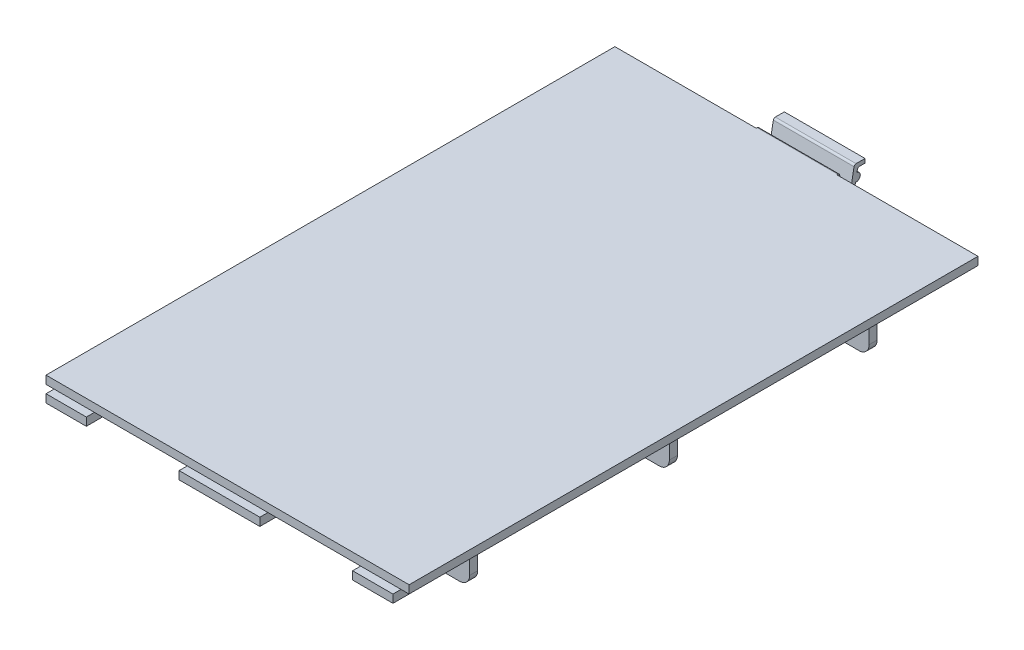
SolidWorks part; units mm, degrees
ref_plane "前视基准面" through (0, 0, 0) normal (0, 0, 1) x (1, 0, 0)
ref_plane "上视基准面" through (0, 0, 0) normal (0, 1, 0) x (1, 0, 0)
ref_plane "右视基准面" through (0, 0, 0) normal (1, 0, 0) x (0, 0, -1)
sketch "Sketch1" plane through (0, 0, 0) normal (0, 1, 0) x (1, 0, 0)
  line L1 (-45, -70.5) -> (45, -70.5)
  line L2 (-45, -70.5) -> (-45, 70.5)
  line L3 (-45, 70.5) -> (45, 70.5)
  line L4 (45, -70.5) -> (45, 70.5)
  line L5 (-45, -70.5) -> (45, 70.5) construction
  line L6 (-45, 70.5) -> (45, -70.5) construction
  point P0 (0, 0)
  dimension "D1" = 141
  dimension "D2" = 90
extrude "Boss-Extrude1" add sketch "Sketch1" along normal blind 2
sketch "Sketch2" plane through (0, 0, 0) normal (0, -1, 0) x (1, 0, 0)
  line L0 (-45, 70.5) -> (45, 70.5) construction
  line L1 (-10, 70.5) -> (10, 70.5)
  line L2 (-10, 70.5) -> (-10, 65.5)
  line L3 (-10, 65.5) -> (10, 65.5)
  line L4 (10, 70.5) -> (10, 65.5)
  line L5 (0, 70.5) -> (0, 40.7579) construction
  line L6 (-43, 70.5) -> (-33, 70.5)
  line L7 (-43, 70.5) -> (-43, 65.5)
  line L8 (-43, 65.5) -> (-33, 65.5)
  line L9 (-33, 70.5) -> (-33, 65.5)
  line L10 (43, 70.5) -> (33, 70.5)
  line L11 (43, 70.5) -> (43, 65.5)
  line L12 (43, 65.5) -> (33, 65.5)
  line L13 (33, 70.5) -> (33, 65.5)
  line L14 (-45, -70.5) -> (-45, 70.5) construction
  line L15 (45, 70.5) -> (45, -70.5) construction
  dimension "D1" = 20
  dimension "D2" = 5
  dimension "D3" = 10
  dimension "D4" = 10
  dimension "D5" = 10
  dimension "D6" = 2
  dimension "D7" = 2
  dimension "D8" = 5
  dimension "D9" = 5
extrude "Boss-Extrude2" add sketch "Sketch2" along normal blind 2
sketch "Sketch3" plane through (0, 0, 70.5) normal (0, 0, 1) x (1, 0, 0)
  line L1 (-43, -2) -> (-33, -2)
  line L2 (-43, -2) -> (-43, 0)
  line L3 (-43, 0) -> (-33, 0)
  line L4 (-33, -2) -> (-33, 0)
  line L5 (-10, -2) -> (10, -2)
  line L6 (-10, -2) -> (-10, 0)
  line L7 (-10, 0) -> (10, 0)
  line L8 (10, -2) -> (10, 0)
  line L9 (33, -2) -> (43, -2)
  line L10 (33, -2) -> (33, 0)
  line L11 (33, 0) -> (43, 0)
  line L12 (43, -2) -> (43, 0)
extrude "Boss-Extrude3" add sketch "Sketch3" along normal blind 2
ref_plane "Plane1" through (0, 0, 0) normal (-1, 0, 0) x (0, 0, 1)
sketch "Sketch4" plane through (0, 0, 0) normal (-1, 0, 0) x (0, 0, 1)
  line L0 (-70.5, 2) -> (-75.5, 2) construction
  line L1 (-73, 2) -> (-73, -7) construction
  line L2 (-72.8177, -7.0168) -> (-71.1463, 2)
  line L3 (-70.5, 0) -> (-72.0126, -8.1596)
  line L4 (-71.1463, 2) -> (-70.5, 2)
  line L5 (-74.8537, 2) -> (-75.5, 2)
  line L6 (-73.1823, -7.0168) -> (-74.8537, 2)
  line L7 (-75.1386, -1.9497) -> (-73.9874, -8.1596)
  line L8 (-77.5, 2) -> (-77.5, 1)
  line L11 (-75.5, 2) -> (-77.5, 2)
  line L13 (-77.5, 1) -> (-75.6854, 1)
  line L14 (-75.5031, 0.0168) -> (-75.6854, 1)
  line L15 (-70.5, 0) -> (-70.5, 2)
  arc A0 (-72.8177, -7.0168) -> (-73.1823, -7.0168) centre (-73, -8) ccw
  arc A1 (-75.5031, 0.0168) -> (-75.1386, -1.9497) centre (-75.3208, -0.9665) ccw
  arc A2 (-72.8177, -7.0165) -> (-73.1823, -7.0165) centre (-73, -8) ccw
  arc A3 (-73.9874, -8.1596) -> (-72.0126, -8.1596) centre (-73, -8) ccw
  point P17 (-73.9874, -8.1596)
  point P18 (-72.0126, -8.1596)
  point P21 (-73, -8)
  dimension "D3" = 2
  dimension "D6" = 2
  dimension "D1" = 5
  dimension "D2" = 10
  dimension "D4" = 1
  dimension "D5" = 2
extrude "Boss-Extrude4" add sketch "Sketch4" along normal mid plane 20 contours L7 A3 L3 L15 L4 L2 A0 L6 L5 L11 L8 L13 L14 A1 region at (0, -7.0404, -72.6895)
fillet "Fillet1" radius 1 1 edges at (0, 0, -70.5)
fillet "Fillet2" radius 0.5 2 edges at (0, 2, -74.8537) (0, 2, -71.1463)
fillet "Fillet3" radius 0.5 1 edges at (0, 1, -75.6854)
sketch "Sketch5" plane through (0, 0, 0) normal (0, -1, 0) x (1, 0, 0)
  line L0 (33, 60.5) -> (33, 50.5)
  line L1 (45, -70.5) -> (10, -70.5) construction
  line L2 (10, 70.5) -> (33, 70.5) construction
  line L3 (-2.5, -1) -> (-28, -1)
  line L4 (33, -50.5) -> (33, -60.5)
  line L5 (0, -81.945) -> (0, -60.5) construction
  line L6 (-33, 70.5) -> (-10, 70.5) construction
  line L7 (-2.5, 60.5) -> (2.5, 60.5)
  line L8 (-2.5, 60.5) -> (-2.5, 49.4375)
  line L9 (-2.5, -60.5) -> (2.5, -60.5)
  line L10 (2.5, 60.5) -> (2.5, 50.5)
  line L11 (-10, -70.5) -> (-45, -70.5) construction
  line L12 (33, -60.5) -> (28, -60.5)
  line L13 (28, -60.5) -> (28, -50.5)
  line L14 (28, 60.5) -> (33, 60.5)
  line L15 (-33, 60.5) -> (-33, 50.325)
  line L16 (-33, -60.5) -> (-28, -60.5)
  line L17 (-28, -60.5) -> (-28, -50.5)
  line L18 (-28, 60.5) -> (-33, 60.5)
  line L19 (45, 0) -> (40, 0) construction
  line L20 (45, 70.5) -> (45, -70.5) construction
  line L21 (-45, -70.5) -> (-45, 70.5) construction
  line L22 (28, -50.5) -> (2.5, -50.5)
  line L23 (40, -1) -> (33, -1)
  line L24 (40, -1) -> (40, 1)
  line L25 (40, 1) -> (33, 1)
  line L26 (-40, -1) -> (-40, 1)
  line L27 (28, -48.5) -> (28, -1)
  line L28 (2.5, -50.5) -> (2.5, -60.5)
  line L29 (40, -50.5) -> (33, -50.5)
  line L30 (40, -50.5) -> (40, -48.5)
  line L31 (40, -48.5) -> (33, -48.5)
  line L32 (-40, -50.5) -> (-40, -48.5)
  line L33 (-33, -50.5) -> (-40, -50.5)
  line L34 (-33, -48.5) -> (-40, -48.5)
  line L35 (40, 48.5) -> (33, 48.5)
  line L36 (40, 48.5) -> (40, 50.5)
  line L37 (40, 50.5) -> (33, 50.5)
  line L38 (-40, 48.5) -> (-40, 50.5)
  line L43 (28, -48.5) -> (2.5, -48.5)
  line L44 (28, -1) -> (2.5, -1)
  line L45 (-2.5, -50.5) -> (-2.5, -60.5)
  line L46 (-28, -48.5) -> (-28, -1)
  line L47 (-33, -50.5) -> (-33, -60.5)
  line L48 (28, 1) -> (2.5, 1)
  line L49 (28, 48.5) -> (2.5, 48.5)
  line L50 (-2.5, -1) -> (-2.5, -48.5)
  line L51 (2.5, -1) -> (2.5, -48.5)
  line L52 (28, 50.5) -> (2.5, 50.5)
  line L54 (-2.5, -50.5) -> (-28, -50.5)
  line L57 (-2.5, -48.5) -> (-28, -48.5)
  line L58 (0, 60.5) -> (0, 83.2655) construction
  line L61 (-2.5, 1) -> (-28, 1)
  line L62 (-2.5, 48.5) -> (-28, 48.5)
  line L63 (-2.5, 49.5625) -> (-28, 50.2) construction
  line L64 (28, 1) -> (28, 48.5)
  line L65 (-2.5, 50.5) -> (-28, 50.5)
  line L66 (-33, 48.5) -> (-40, 48.5)
  line L67 (-33, 48.675) -> (-40, 48.5) construction
  line L68 (-33, 50.325) -> (-40, 50.5) construction
  line L69 (-33, 50.5) -> (-40, 50.5)
  line L70 (33, 48.5) -> (33, 1)
  line L71 (28, 50.5) -> (28, 60.5)
  line L72 (2.5, 48.5) -> (2.5, 1)
  line L73 (-2.5, 48.5) -> (-2.5, 1)
  line L74 (-28, 50.2) -> (-28, 60.5)
  line L75 (-33, 48.675) -> (-33, 1)
  line L76 (-33, -1) -> (-40, -1)
  line L78 (-40, 0) -> (-45, 0) construction
  line L80 (-33, 1) -> (-40, 1)
  line L81 (-33, -1) -> (-33, -48.5)
  line L82 (-28, 1) -> (-28, 48.5)
  line L83 (33, -1) -> (33, -48.5)
  point P10 (0, 0.6603)
  point P32 (0, 0)
  point P37 (0, -49.5)
  point P42 (0, 49.5)
  dimension "D1" = 10
  dimension "D2" = 10
  dimension "D3" = 10
  dimension "D4" = 10
  dimension "D5" = 5
  dimension "D6" = 2.5
  dimension "D7" = 5
  dimension "D8" = 5
  dimension "D9" = 5
  dimension "D10" = 2
  dimension "D11" = 2
  dimension "D12" = 10
  dimension "D13" = 2
  dimension "D14" = 10
extrude "Boss-Extrude5" add sketch "Sketch5" along normal blind 11 contours L83 L23 L24 L25 L70 L35 L36 L37 L0 L14 L71 L52 L10 L7 L8 L65 L74 L18 L15 L69 L38 L66 L75 L80 L26 L76 L81 L34 L32 L33 L47 L16 L17 L54 L45 L9 L28 L22 L13 L12 L4 L29 L30 region at (0, 0, 0)
fillet "Fillet4" radius 2.5 12 edges at (-40, -11, 49.5) (40, -11, 49.5) (40, -11, 0) (-40, -11, 0) (-40, -11, -49.5) (40, -11, -49.5) (-30.5, -11, 60.5) (0, -11, 60.5) (30.5, -11, 60.5) (0, -11, -60.5) (-30.5, -11, -60.5) (30.5, -11, -60.5)
